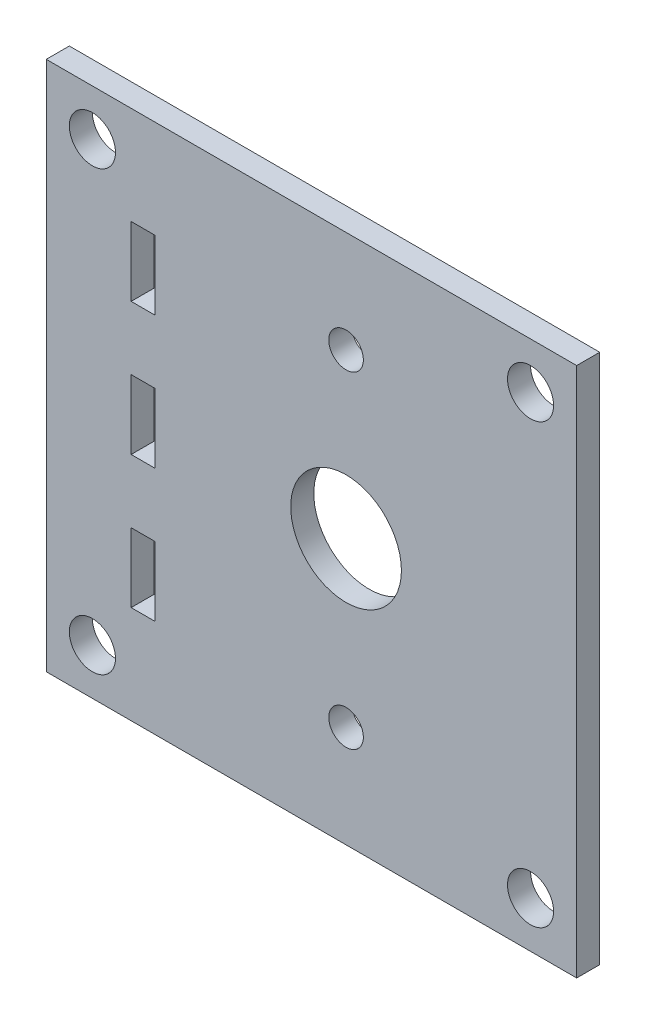
SolidWorks part; units mm, degrees
ref_plane "Front Plane" through (0, 0, 0) normal (0, 0, 1) x (1, 0, 0)
ref_plane "Top Plane" through (0, 0, 0) normal (0, 1, 0) x (1, 0, 0)
ref_plane "Right Plane" through (0, 0, 0) normal (1, 0, 0) x (0, 0, -1)
sketch "Sketch1" plane through (0, 0, 0) normal (0, 0, 1) x (1, 0, 0)
  line L0 (0, 73.025) -> (0, -73.025) construction
  line L1 (63.5, 73.025) -> (-82.55, 73.025)
  line L2 (63.5, 73.025) -> (63.5, -73.025)
  line L3 (63.5, -73.025) -> (-82.55, -73.025)
  line L4 (-82.55, 73.025) -> (-82.55, -73.025)
  line L5 (0, 45) -> (0, -45) construction
  line L6 (-55.88, 73.025) -> (-55.88, 36.5125) construction
  line L7 (-59.182, -9.525) -> (-52.578, -9.525)
  line L8 (-59.182, -9.525) -> (-59.182, 9.525)
  line L9 (-59.182, 9.525) -> (-52.578, 9.525)
  line L10 (-52.578, -9.525) -> (-52.578, 9.525)
  line L11 (-59.182, -9.525) -> (-52.578, 9.525) construction
  line L12 (-59.182, 9.525) -> (-52.578, -9.525) construction
  line L13 (-59.182, 46.0375) -> (-52.578, 46.0375)
  line L14 (-59.182, 46.0375) -> (-59.182, 26.9875)
  line L15 (-59.182, 26.9875) -> (-52.578, 26.9875)
  line L16 (-52.578, 46.0375) -> (-52.578, 26.9875)
  line L17 (-59.182, 46.0375) -> (-52.578, 26.9875) construction
  line L18 (-59.182, 26.9875) -> (-52.578, 46.0375) construction
  line L19 (-59.182, -26.9875) -> (-52.578, -26.9875)
  line L20 (-59.182, -26.9875) -> (-59.182, -46.0375)
  line L21 (-59.182, -46.0375) -> (-52.578, -46.0375)
  line L22 (-52.578, -26.9875) -> (-52.578, -46.0375)
  line L23 (-59.182, -26.9875) -> (-52.578, -46.0375) construction
  line L24 (-59.182, -46.0375) -> (-52.578, -26.9875) construction
  line L25 (-55.88, 36.5125) -> (-55.88, 0) construction
  line L26 (-55.88, 0) -> (-55.88, -36.5125) construction
  line L27 (-55.88, -36.5125) -> (-55.88, -73.025) construction
  circle A0 centre (50.8, 60.325) radius 6.35
  circle A1 centre (50.8, -60.325) radius 6.35
  circle A2 centre (0, 0) radius 15.24
  circle A3 centre (0, 45) radius 4.7625
  circle A4 centre (0, -45) radius 4.7625
  circle A5 centre (-69.85, 60.325) radius 6.35
  circle A6 centre (-69.85, -60.325) radius 6.35
  point P0 (0, 0)
  point P14 (0, 0)
  point P19 (0, 0)
  point P24 (-55.88, 36.5125)
  point P28 (-55.88, 0)
  point P34 (-55.88, -36.5125)
  dimension "D2" = 12.7
  dimension "D6" = 30.48
  dimension "D8" = 9.525
  dimension "D1" = 146.05
  dimension "D3" = 12.7
  dimension "D4" = 12.7
  dimension "D5" = 50.8
  dimension "D7" = 90
  dimension "D9" = 12.7
  dimension "D10" = 82.55
  dimension "D11" = 12.7
  dimension "D12" = 19.05
  dimension "D13" = 6.604
  dimension "D14" = 55.88
extrude "Boss-Extrude1" add sketch "Sketch1" along normal mid plane 6.35
